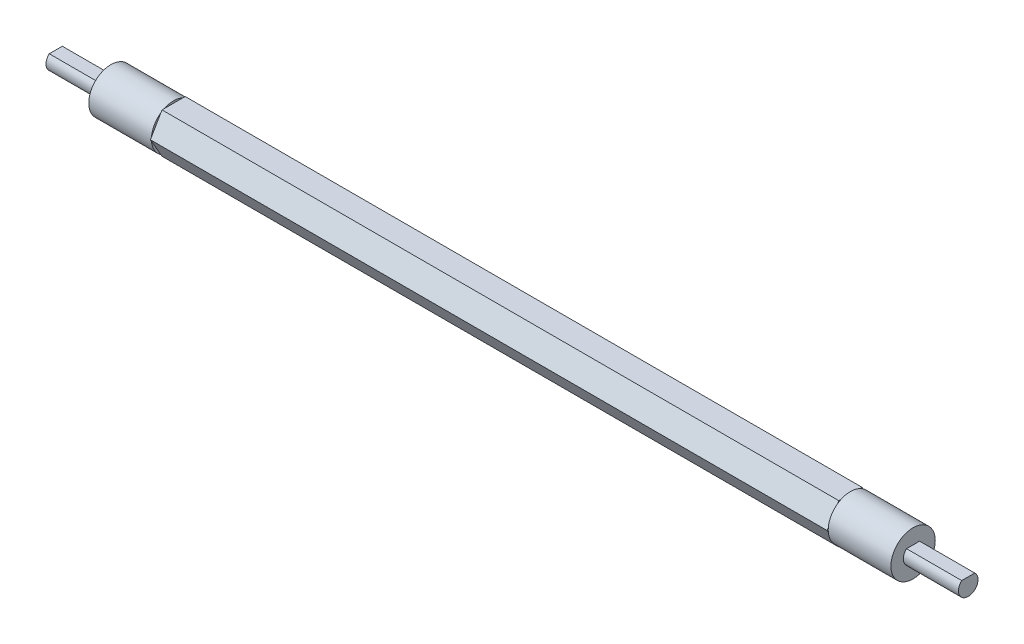
SolidWorks part; units mm, degrees
material "ABS"
ref_plane "Front Plane" through (0, 0, 0) normal (0, 0, 1) x (1, 0, 0)
ref_plane "Top Plane" through (0, 0, 0) normal (0, 1, 0) x (1, 0, 0)
ref_plane "Right Plane" through (0, 0, 0) normal (1, 0, 0) x (0, 0, -1)
sketch "Sketch1" plane through (0, 0, 0) normal (1, 0, 0) x (0, 0, -1)
  line L1 (4.625, 0) -> (2.3125, 4.0054)
  line L2 (2.3125, 4.0054) -> (-2.3125, 4.0054)
  line L3 (-2.3125, 4.0054) -> (-4.625, 0)
  line L4 (-4.625, 0) -> (-2.3125, -4.0054)
  line L5 (-2.3125, -4.0054) -> (2.3125, -4.0054)
  line L6 (2.3125, -4.0054) -> (4.625, 0)
  circle A0 centre (0, 0) radius 4.625 construction
  circle A1 centre (0, 0) radius 4.425
  point P10 (0, 0)
  point P11 (0, 0)
  point P12 (2.2125, 3.8322)
  dimension "D1" = 8.85
  dimension "D2" = 9.25
extrude "Boss-Extrude1" add sketch "Sketch1" along normal mid plane 135 contours L1 A1 L2 L3 L4 L5 L6 | A1 L3 L4 | A1 L2 L3 | A1 L1 L2 | A1 L6 L1 | A1 L5 L6 | A1 L4 L5 region at (0, 0, -4.4882) region at (0, 0, 0) region at (0, 3.8869, -2.2441) region at (0, -3.8869, -2.2441) region at (0, 3.8869, 2.2441) region at (0, -3.8869, 2.2441) region at (0, 0, 4.4882)
extrude "Boss-Extrude2" add sketch "Sketch1<3>" along normal blind 12.5 from offset 67.5 contours L2 A1 | L1 A1 | L6 A1 | L5 A1 | L4 A1 | L3 A1 | L5 L6 L1 L2 L3 L4 region at (0, 0, 0) region at (0, 2.087, -3.6147) region at (0, -2.087, -3.6147) region at (0, 4.1739, 0) region at (0, -4.1739, 0) region at (0, 2.087, 3.6147) region at (0, -2.087, 3.6147)
sketch "Sketch1<3>" plane through (0, 0, 0) normal (1, 0, 0) x (0, 0, -1) same geometry as "Sketch1"
sketch "Sketch4" plane through (80, 0, 0) normal (1, 0, 0) x (0, 0, -1)
  line L0 (-1.3038, 1.45) -> (1.3038, 1.45)
  circle A1 centre (0, 0) radius 1.95
  circle A2 centre (0, 0) radius 4.425
  circle A3 centre (0, 0) radius 4.425
  dimension "D1" = 3.9
  dimension "D3" = 0.5
  dimension "D2" = 0
extrude "Boss-Extrude4" add sketch "Sketch4" along normal blind 11 contours L0 A1 region at (80, -0.1337, 0)
mirror "Mirror2" about plane through (0, 0, 0) normal (1, 0, 0) of "Boss-Extrude4", "Boss-Extrude2"
